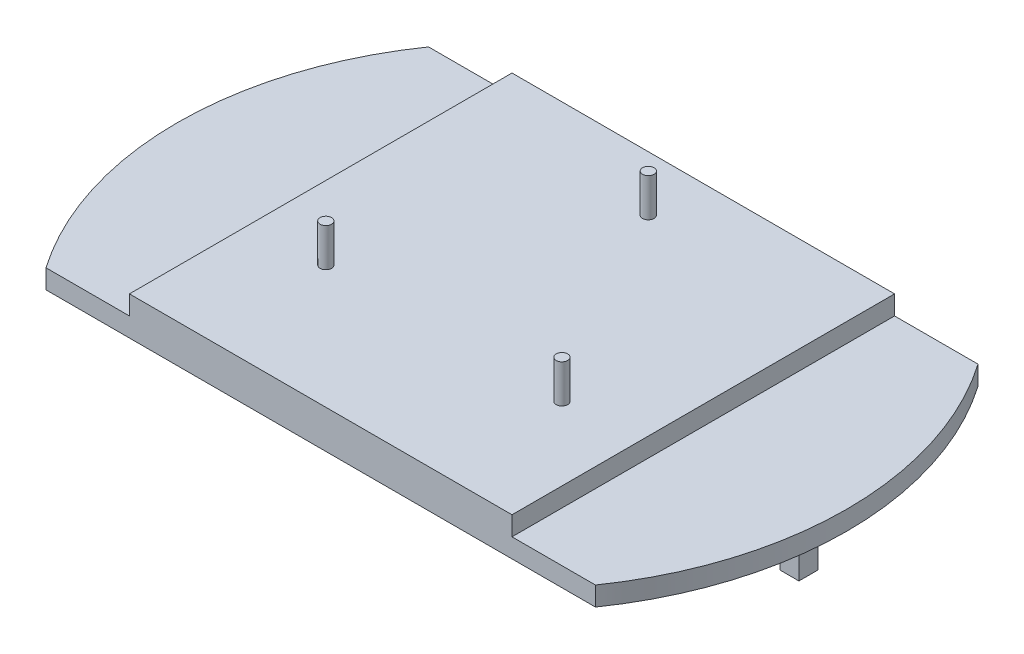
SolidWorks part; units mm, degrees
ref_plane "前基準面" through (0, 0, 0) normal (0, 0, 1) x (1, 0, 0)
ref_plane "上基準面" through (0, 0, 0) normal (0, 1, 0) x (1, 0, 0)
ref_plane "右基準面" through (0, 0, 0) normal (1, 0, 0) x (0, 0, -1)
sketch "草圖1" plane through (0, 0, 0) normal (0, 1, 0) x (1, 0, 0)
  line L0 (0, 0) -> (0, 28.4634) construction
  line L1 (0, 0) -> (-24.65, -14.2317) construction
  line L2 (0, 0) -> (24.65, -14.2317) construction
  line L4 (100, 100) -> (-100, 100)
  line L5 (100, 100) -> (100, -100)
  line L6 (100, -100) -> (-100, -100)
  line L7 (-100, 100) -> (-100, -100)
  line L8 (0, -100) -> (0, 100) construction
  line L9 (100, 0) -> (-100, 0) construction
  circle A0 centre (0, 0) radius 28.4634 construction
  circle A1 centre (0, 28.4634) radius 10 construction
  circle A2 centre (24.65, -14.2317) radius 10 construction
  circle A3 centre (-24.65, -14.2317) radius 10 construction
  circle A5 centre (0, 0) radius 100 construction
  dimension "D3" = 49.3
  dimension "D4" = 20
  dimension "D6" = 200
  dimension "D1" = 120
  dimension "D2" = 120
extrude "填料-伸長1" add sketch "草圖1" along normal blind 10
sketch "草圖2" plane through (0, 0, 0) normal (0, -1, 0) x (1, 0, 0)
  line L0 (-150, 0) -> (150, 0) construction
  line L1 (143.6141, 100) -> (-143.6141, 100)
  line L2 (143.6141, -100) -> (-143.6141, -100)
  line L7 (-100, 100) -> (-100, -100)
  line L8 (-100, 100) -> (-100, -100) construction
  line L9 (100, 100) -> (-100, 100)
  line L10 (100, 100) -> (-100, 100) construction
  line L11 (100, -100) -> (100, 100)
  line L12 (100, -100) -> (100, 100) construction
  line L13 (-100, -100) -> (100, -100)
  line L14 (-100, -100) -> (100, -100) construction
  circle A0 centre (-150, 0) radius 5
  circle A1 centre (150, 0) radius 5
  arc A2 (143.6141, -100) -> (143.6141, 100) centre (0, 0) ccw
  arc A3 (-143.6141, 100) -> (-143.6141, -100) centre (0, 0) ccw
  point P3 (0, 0)
  dimension "D2" = 10
  dimension "D3" = 350
  dimension "D1" = 300
  dimension "D4" = 0
extrude "填料-伸長2" add sketch "草圖2" along normal blind 10
sketch "草圖3" plane through (0, -10, 0) normal (0, -1, 0) x (1, 0, 0)
  line L0 (0, -112.955) -> (0, 120.2774) construction
  line L1 (-155, -5) -> (-145, -5)
  line L2 (-155, -5) -> (-155, 5)
  line L3 (-155, 5) -> (-145, 5)
  line L4 (-145, -5) -> (-145, 5)
  line L5 (-150, 5) -> (-150, -5) construction
  line L6 (-155, 0) -> (-145, 0) construction
  line L7 (155, 0) -> (145, 0) construction
  line L8 (150, 5) -> (150, -5) construction
  line L9 (145, -5) -> (145, 5)
  line L10 (155, 5) -> (145, 5)
  line L11 (155, -5) -> (155, 5)
  line L12 (155, -5) -> (145, -5)
  circle A0 centre (-150, 0) radius 5 construction
  circle A2 centre (150, 0) radius 5 construction
  circle A3 centre (150, 0) radius 5 construction
  dimension "D1" = 10
  dimension "D2" = 10
extrude "填料-伸長3" add sketch "草圖3" along normal blind 30 and the other way up to surface (10 mm away) other way up to face at (129.6535, 0, 0)
sketch "草圖4" plane through (0, 10, 0) normal (0, 1, 0) x (1, 0, 0)
  circle A6 centre (0, 71.25) radius 3
  circle A7 centre (61.7043, -35.625) radius 3
  circle A8 centre (-61.7043, -35.625) radius 3
  point P0 (0, 71.25)
  point P16 (0, 0)
  dimension "D1" = 6
  dimension "D4" = 6
  dimension "D3" = 71.25
  dimension "D2" = 3
extrude "填料-伸長4" add sketch "草圖4" along normal blind 20
